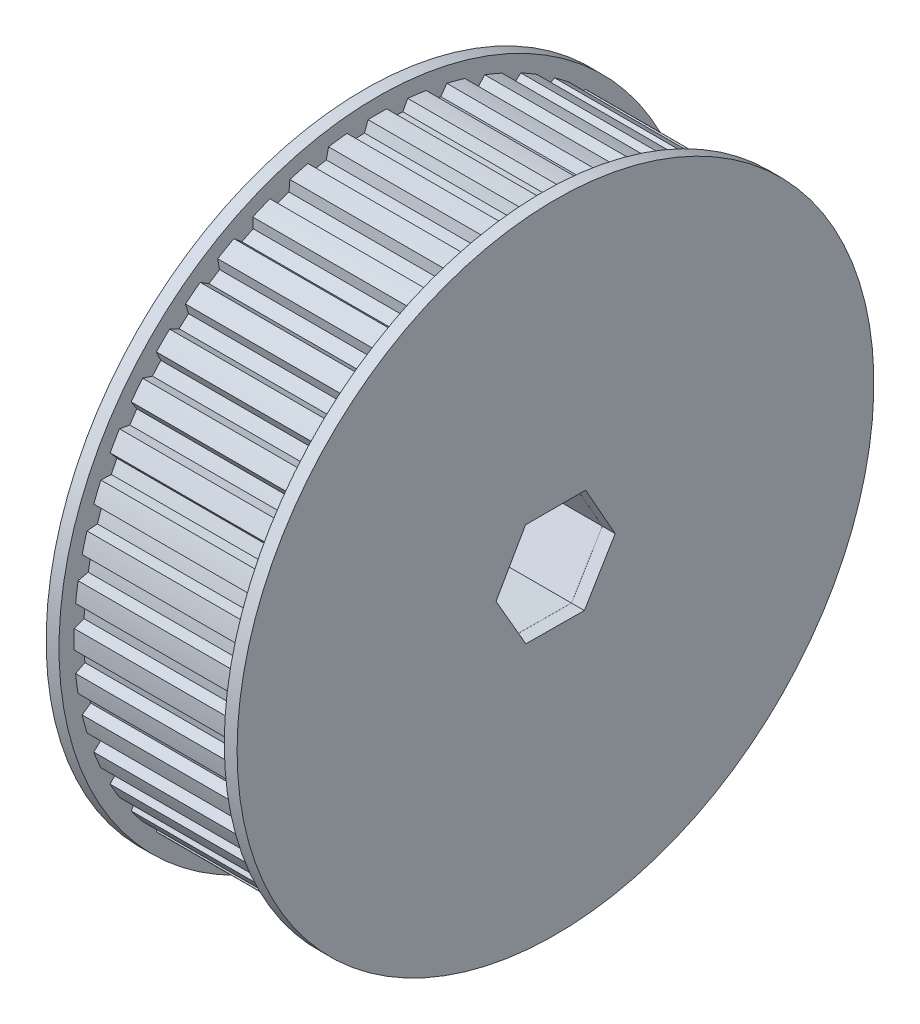
SolidWorks part; units mm, degrees
ref_plane "Front Plane" through (0, 0, 0) normal (0, 0, 1) x (1, 0, 0)
ref_plane "Top Plane" through (0, 0, 0) normal (0, 1, 0) x (1, 0, 0)
ref_plane "Right Plane" through (0, 0, 0) normal (1, 0, 0) x (0, 0, -1)
ref_plane "Plane1" through (0, 0, 0) normal (0, 0, -1) x (-1, 0, 0)
sketch "Sketch1" plane through (0, 0, 0) normal (0, 0, -1) x (-1, 0, 0)
  line L0 (-20.5, 37.625) -> (-20.5, 0)
  line L1 (-20.5, 0) -> (0, 0)
  line L2 (0, 0) -> (0, 37.625)
  line L3 (0, 37.625) -> (-20.5, 37.625)
  line L4 (-20.5, 0) -> (0, 0) construction
revolve "Revolve1" add sketch "Sketch1" angle 360 about L4 reverse direction yes
sketch "Sketch2" plane through (0, 0, 0) normal (-1, 0, 0) x (0, 0, 1)
  line L0 (-37.6072, 1.1569) -> (-36.3898, 1.6)
  line L1 (-36.2874, 3.1635) -> (-37.4365, 3.7617)
  arc A0 (-37.4365, 3.7617) -> (-37.6072, 1.1569) centre (0, 0) ccw
  arc A1 (-36.3898, 1.6) -> (-36.2874, 3.1635) centre (0, 0) cw
extrude "Cut-Extrude1" cut sketch "Sketch2" against normal through all
sketch "Sketch3" plane through (0, 0, 0) normal (-1, 0, 0) x (0, 0, 1)
  line L0 (-37.1345, 6.0557) -> (-35.8697, 6.3361)
  line L1 (-35.564, 7.8729) -> (-36.6252, 8.616)
  arc A0 (-36.6252, 8.616) -> (-37.1345, 6.0557) centre (0, 0) ccw
  arc A1 (-35.8697, 6.3361) -> (-35.564, 7.8729) centre (0, 0) cw
extrude "Cut-Extrude2" cut sketch "Sketch3" against normal through all
sketch "Sketch4" plane through (0, 0, 0) normal (-1, 0, 0) x (0, 0, 1)
  line L0 (-36.0263, 10.851) -> (-34.7358, 10.9639)
  line L1 (-34.2321, 12.4476) -> (-35.1873, 13.3228)
  arc A0 (-35.1873, 13.3228) -> (-36.0263, 10.851) centre (0, 0) ccw
  arc A1 (-34.7358, 10.9639) -> (-34.2321, 12.4476) centre (0, 0) cw
extrude "Cut-Extrude3" cut sketch "Sketch4" against normal through all
sketch "Sketch5" plane through (0, 0, 0) normal (-1, 0, 0) x (0, 0, 1)
  line L0 (-34.3018, 15.4605) -> (-33.0075, 15.404)
  line L1 (-32.3145, 16.8093) -> (-33.1473, 17.8017)
  arc A0 (-33.1473, 17.8017) -> (-34.3018, 15.4605) centre (0, 0) ccw
  arc A1 (-33.0075, 15.404) -> (-32.3145, 16.8093) centre (0, 0) cw
extrude "Cut-Extrude4" cut sketch "Sketch5" against normal through all
sketch "Sketch6" plane through (0, 0, 0) normal (-1, 0, 0) x (0, 0, 1)
  line L0 (-31.9903, 19.8055) -> (-30.7145, 19.5806)
  line L1 (-29.844, 20.8834) -> (-30.5401, 21.976)
  arc A0 (-30.5401, 21.976) -> (-31.9903, 19.8055) centre (0, 0) ccw
  arc A1 (-30.7145, 19.5806) -> (-29.844, 20.8834) centre (0, 0) cw
extrude "Cut-Extrude5" cut sketch "Sketch6" against normal through all
sketch "Sketch7" plane through (0, 0, 0) normal (-1, 0, 0) x (0, 0, 1)
  line L0 (-29.1315, 23.8117) -> (-27.896, 23.4221)
  line L1 (-26.8629, 24.6001) -> (-27.4104, 25.7743)
  arc A0 (-27.4104, 25.7743) -> (-29.1315, 23.8117) centre (0, 0) ccw
  arc A1 (-27.896, 23.4221) -> (-26.8629, 24.6001) centre (0, 0) cw
extrude "Cut-Extrude6" cut sketch "Sketch7" against normal through all
sketch "Sketch8" plane through (0, 0, 0) normal (-1, 0, 0) x (0, 0, 1)
  line L0 (-25.7743, 27.4104) -> (-24.6001, 26.8629)
  line L1 (-23.4221, 27.896) -> (-23.8117, 29.1315)
  arc A0 (-23.8117, 29.1315) -> (-25.7743, 27.4104) centre (0, 0) ccw
  arc A1 (-24.6001, 26.8629) -> (-23.4221, 27.896) centre (0, 0) cw
extrude "Cut-Extrude7" cut sketch "Sketch8" against normal through all
sketch "Sketch9" plane through (0, 0, 0) normal (-1, 0, 0) x (0, 0, 1)
  line L0 (-21.976, 30.5401) -> (-20.8834, 29.844)
  line L1 (-19.5806, 30.7145) -> (-19.8055, 31.9903)
  arc A0 (-19.8055, 31.9903) -> (-21.976, 30.5401) centre (0, 0) ccw
  arc A1 (-20.8834, 29.844) -> (-19.5806, 30.7145) centre (0, 0) cw
extrude "Cut-Extrude8" cut sketch "Sketch9" against normal through all
sketch "Sketch10" plane through (0, 0, 0) normal (-1, 0, 0) x (0, 0, 1)
  line L0 (-17.8017, 33.1473) -> (-16.8093, 32.3145)
  line L1 (-15.404, 33.0075) -> (-15.4605, 34.3018)
  arc A0 (-15.4605, 34.3018) -> (-17.8017, 33.1473) centre (0, 0) ccw
  arc A1 (-16.8093, 32.3145) -> (-15.404, 33.0075) centre (0, 0) cw
extrude "Cut-Extrude9" cut sketch "Sketch10" against normal through all
sketch "Sketch11" plane through (0, 0, 0) normal (-1, 0, 0) x (0, 0, 1)
  line L0 (-13.3228, 35.1873) -> (-12.4476, 34.2321)
  line L1 (-10.9639, 34.7358) -> (-10.851, 36.0263)
  arc A0 (-10.851, 36.0263) -> (-13.3228, 35.1873) centre (0, 0) ccw
  arc A1 (-12.4476, 34.2321) -> (-10.9639, 34.7358) centre (0, 0) cw
extrude "Cut-Extrude10" cut sketch "Sketch11" against normal through all
sketch "Sketch12" plane through (0, 0, 0) normal (-1, 0, 0) x (0, 0, 1)
  line L0 (-8.616, 36.6252) -> (-7.8729, 35.564)
  line L1 (-6.3361, 35.8697) -> (-6.0557, 37.1345)
  arc A0 (-6.0557, 37.1345) -> (-8.616, 36.6252) centre (0, 0) ccw
  arc A1 (-7.8729, 35.564) -> (-6.3361, 35.8697) centre (0, 0) cw
extrude "Cut-Extrude11" cut sketch "Sketch12" against normal through all
sketch "Sketch13" plane through (0, 0, 0) normal (-1, 0, 0) x (0, 0, 1)
  line L0 (-3.7617, 37.4365) -> (-3.1635, 36.2874)
  line L1 (-1.6, 36.3898) -> (-1.1569, 37.6072)
  arc A0 (-1.1569, 37.6072) -> (-3.7617, 37.4365) centre (0, 0) ccw
  arc A1 (-3.1635, 36.2874) -> (-1.6, 36.3898) centre (0, 0) cw
extrude "Cut-Extrude12" cut sketch "Sketch13" against normal through all
sketch "Sketch14" plane through (0, 0, 0) normal (-1, 0, 0) x (0, 0, 1)
  line L0 (1.1569, 37.6072) -> (1.6, 36.3898)
  line L1 (3.1635, 36.2874) -> (3.7617, 37.4365)
  arc A0 (3.7617, 37.4365) -> (1.1569, 37.6072) centre (0, 0) ccw
  arc A1 (1.6, 36.3898) -> (3.1635, 36.2874) centre (0, 0) cw
extrude "Cut-Extrude13" cut sketch "Sketch14" against normal through all
sketch "Sketch15" plane through (0, 0, 0) normal (-1, 0, 0) x (0, 0, 1)
  line L0 (6.0557, 37.1345) -> (6.3361, 35.8697)
  line L1 (7.8729, 35.564) -> (8.616, 36.6252)
  arc A0 (8.616, 36.6252) -> (6.0557, 37.1345) centre (0, 0) ccw
  arc A1 (6.3361, 35.8697) -> (7.8729, 35.564) centre (0, 0) cw
extrude "Cut-Extrude14" cut sketch "Sketch15" against normal through all
sketch "Sketch16" plane through (0, 0, 0) normal (-1, 0, 0) x (0, 0, 1)
  line L0 (10.851, 36.0263) -> (10.9639, 34.7358)
  line L1 (12.4476, 34.2321) -> (13.3228, 35.1873)
  arc A0 (13.3228, 35.1873) -> (10.851, 36.0263) centre (0, 0) ccw
  arc A1 (10.9639, 34.7358) -> (12.4476, 34.2321) centre (0, 0) cw
extrude "Cut-Extrude15" cut sketch "Sketch16" against normal through all
sketch "Sketch17" plane through (0, 0, 0) normal (-1, 0, 0) x (0, 0, 1)
  line L0 (15.4605, 34.3018) -> (15.404, 33.0075)
  line L1 (16.8093, 32.3145) -> (17.8017, 33.1473)
  arc A0 (17.8017, 33.1473) -> (15.4605, 34.3018) centre (0, 0) ccw
  arc A1 (15.404, 33.0075) -> (16.8093, 32.3145) centre (0, 0) cw
extrude "Cut-Extrude16" cut sketch "Sketch17" against normal through all
sketch "Sketch18" plane through (0, 0, 0) normal (-1, 0, 0) x (0, 0, 1)
  line L0 (19.8055, 31.9903) -> (19.5806, 30.7145)
  line L1 (20.8834, 29.844) -> (21.976, 30.5401)
  arc A0 (21.976, 30.5401) -> (19.8055, 31.9903) centre (0, 0) ccw
  arc A1 (19.5806, 30.7145) -> (20.8834, 29.844) centre (0, 0) cw
extrude "Cut-Extrude17" cut sketch "Sketch18" against normal through all
sketch "Sketch19" plane through (0, 0, 0) normal (-1, 0, 0) x (0, 0, 1)
  line L0 (23.8117, 29.1315) -> (23.4221, 27.896)
  line L1 (24.6001, 26.8629) -> (25.7743, 27.4104)
  arc A0 (25.7743, 27.4104) -> (23.8117, 29.1315) centre (0, 0) ccw
  arc A1 (23.4221, 27.896) -> (24.6001, 26.8629) centre (0, 0) cw
extrude "Cut-Extrude18" cut sketch "Sketch19" against normal through all
sketch "Sketch20" plane through (0, 0, 0) normal (-1, 0, 0) x (0, 0, 1)
  line L0 (27.4104, 25.7743) -> (26.8629, 24.6001)
  line L1 (27.896, 23.4221) -> (29.1315, 23.8117)
  arc A0 (29.1315, 23.8117) -> (27.4104, 25.7743) centre (0, 0) ccw
  arc A1 (26.8629, 24.6001) -> (27.896, 23.4221) centre (0, 0) cw
extrude "Cut-Extrude19" cut sketch "Sketch20" against normal through all
sketch "Sketch21" plane through (0, 0, 0) normal (-1, 0, 0) x (0, 0, 1)
  line L0 (30.5401, 21.976) -> (29.844, 20.8834)
  line L1 (30.7145, 19.5806) -> (31.9903, 19.8055)
  arc A0 (31.9903, 19.8055) -> (30.5401, 21.976) centre (0, 0) ccw
  arc A1 (29.844, 20.8834) -> (30.7145, 19.5806) centre (0, 0) cw
extrude "Cut-Extrude20" cut sketch "Sketch21" against normal through all
sketch "Sketch22" plane through (0, 0, 0) normal (-1, 0, 0) x (0, 0, 1)
  line L0 (33.1473, 17.8017) -> (32.3145, 16.8093)
  line L1 (33.0075, 15.404) -> (34.3018, 15.4605)
  arc A0 (34.3018, 15.4605) -> (33.1473, 17.8017) centre (0, 0) ccw
  arc A1 (32.3145, 16.8093) -> (33.0075, 15.404) centre (0, 0) cw
extrude "Cut-Extrude21" cut sketch "Sketch22" against normal through all
sketch "Sketch23" plane through (0, 0, 0) normal (-1, 0, 0) x (0, 0, 1)
  line L0 (35.1873, 13.3228) -> (34.2321, 12.4476)
  line L1 (34.7358, 10.9639) -> (36.0263, 10.851)
  arc A0 (36.0263, 10.851) -> (35.1873, 13.3228) centre (0, 0) ccw
  arc A1 (34.2321, 12.4476) -> (34.7358, 10.9639) centre (0, 0) cw
extrude "Cut-Extrude22" cut sketch "Sketch23" against normal through all
sketch "Sketch24" plane through (0, 0, 0) normal (-1, 0, 0) x (0, 0, 1)
  line L0 (36.6252, 8.616) -> (35.564, 7.8729)
  line L1 (35.8697, 6.3361) -> (37.1345, 6.0557)
  arc A0 (37.1345, 6.0557) -> (36.6252, 8.616) centre (0, 0) ccw
  arc A1 (35.564, 7.8729) -> (35.8697, 6.3361) centre (0, 0) cw
extrude "Cut-Extrude23" cut sketch "Sketch24" against normal through all
sketch "Sketch25" plane through (0, 0, 0) normal (-1, 0, 0) x (0, 0, 1)
  line L0 (37.4365, 3.7617) -> (36.2874, 3.1635)
  line L1 (36.3898, 1.6) -> (37.6072, 1.1569)
  arc A0 (37.6072, 1.1569) -> (37.4365, 3.7617) centre (0, 0) ccw
  arc A1 (36.2874, 3.1635) -> (36.3898, 1.6) centre (0, 0) cw
extrude "Cut-Extrude24" cut sketch "Sketch25" against normal through all
sketch "Sketch26" plane through (0, 0, 0) normal (-1, 0, 0) x (0, 0, 1)
  line L0 (37.6072, -1.1569) -> (36.3898, -1.6)
  line L1 (36.2874, -3.1635) -> (37.4365, -3.7617)
  arc A0 (37.4365, -3.7617) -> (37.6072, -1.1569) centre (0, 0) ccw
  arc A1 (36.3898, -1.6) -> (36.2874, -3.1635) centre (0, 0) cw
extrude "Cut-Extrude25" cut sketch "Sketch26" against normal through all
sketch "Sketch27" plane through (0, 0, 0) normal (-1, 0, 0) x (0, 0, 1)
  line L0 (37.1345, -6.0557) -> (35.8697, -6.3361)
  line L1 (35.564, -7.8729) -> (36.6252, -8.616)
  arc A0 (36.6252, -8.616) -> (37.1345, -6.0557) centre (0, 0) ccw
  arc A1 (35.8697, -6.3361) -> (35.564, -7.8729) centre (0, 0) cw
extrude "Cut-Extrude26" cut sketch "Sketch27" against normal through all
sketch "Sketch28" plane through (0, 0, 0) normal (-1, 0, 0) x (0, 0, 1)
  line L0 (36.0263, -10.851) -> (34.7358, -10.9639)
  line L1 (34.2321, -12.4476) -> (35.1873, -13.3228)
  arc A0 (35.1873, -13.3228) -> (36.0263, -10.851) centre (0, 0) ccw
  arc A1 (34.7358, -10.9639) -> (34.2321, -12.4476) centre (0, 0) cw
extrude "Cut-Extrude27" cut sketch "Sketch28" against normal through all
sketch "Sketch29" plane through (0, 0, 0) normal (-1, 0, 0) x (0, 0, 1)
  line L0 (34.3018, -15.4605) -> (33.0075, -15.404)
  line L1 (32.3145, -16.8093) -> (33.1473, -17.8017)
  arc A0 (33.1473, -17.8017) -> (34.3018, -15.4605) centre (0, 0) ccw
  arc A1 (33.0075, -15.404) -> (32.3145, -16.8093) centre (0, 0) cw
extrude "Cut-Extrude28" cut sketch "Sketch29" against normal through all
sketch "Sketch30" plane through (0, 0, 0) normal (-1, 0, 0) x (0, 0, 1)
  line L0 (31.9903, -19.8055) -> (30.7145, -19.5806)
  line L1 (29.844, -20.8834) -> (30.5401, -21.976)
  arc A0 (30.5401, -21.976) -> (31.9903, -19.8055) centre (0, 0) ccw
  arc A1 (30.7145, -19.5806) -> (29.844, -20.8834) centre (0, 0) cw
extrude "Cut-Extrude29" cut sketch "Sketch30" against normal through all
sketch "Sketch31" plane through (0, 0, 0) normal (-1, 0, 0) x (0, 0, 1)
  line L0 (29.1315, -23.8117) -> (27.896, -23.4221)
  line L1 (26.8629, -24.6001) -> (27.4104, -25.7743)
  arc A0 (27.4104, -25.7743) -> (29.1315, -23.8117) centre (0, 0) ccw
  arc A1 (27.896, -23.4221) -> (26.8629, -24.6001) centre (0, 0) cw
extrude "Cut-Extrude30" cut sketch "Sketch31" against normal through all
sketch "Sketch32" plane through (0, 0, 0) normal (-1, 0, 0) x (0, 0, 1)
  line L0 (25.7743, -27.4104) -> (24.6001, -26.8629)
  line L1 (23.4221, -27.896) -> (23.8117, -29.1315)
  arc A0 (23.8117, -29.1315) -> (25.7743, -27.4104) centre (0, 0) ccw
  arc A1 (24.6001, -26.8629) -> (23.4221, -27.896) centre (0, 0) cw
extrude "Cut-Extrude31" cut sketch "Sketch32" against normal through all
sketch "Sketch33" plane through (0, 0, 0) normal (-1, 0, 0) x (0, 0, 1)
  line L0 (21.976, -30.5401) -> (20.8834, -29.844)
  line L1 (19.5806, -30.7145) -> (19.8055, -31.9903)
  arc A0 (19.8055, -31.9903) -> (21.976, -30.5401) centre (0, 0) ccw
  arc A1 (20.8834, -29.844) -> (19.5806, -30.7145) centre (0, 0) cw
extrude "Cut-Extrude32" cut sketch "Sketch33" against normal through all
sketch "Sketch34" plane through (0, 0, 0) normal (-1, 0, 0) x (0, 0, 1)
  line L0 (17.8017, -33.1473) -> (16.8093, -32.3145)
  line L1 (15.404, -33.0075) -> (15.4605, -34.3018)
  arc A0 (15.4605, -34.3018) -> (17.8017, -33.1473) centre (0, 0) ccw
  arc A1 (16.8093, -32.3145) -> (15.404, -33.0075) centre (0, 0) cw
extrude "Cut-Extrude33" cut sketch "Sketch34" against normal through all
sketch "Sketch35" plane through (0, 0, 0) normal (-1, 0, 0) x (0, 0, 1)
  line L0 (13.3228, -35.1873) -> (12.4476, -34.2321)
  line L1 (10.9639, -34.7358) -> (10.851, -36.0263)
  arc A0 (10.851, -36.0263) -> (13.3228, -35.1873) centre (0, 0) ccw
  arc A1 (12.4476, -34.2321) -> (10.9639, -34.7358) centre (0, 0) cw
extrude "Cut-Extrude34" cut sketch "Sketch35" against normal through all
sketch "Sketch36" plane through (0, 0, 0) normal (-1, 0, 0) x (0, 0, 1)
  line L0 (8.616, -36.6252) -> (7.8729, -35.564)
  line L1 (6.3361, -35.8697) -> (6.0557, -37.1345)
  arc A0 (6.0557, -37.1345) -> (8.616, -36.6252) centre (0, 0) ccw
  arc A1 (7.8729, -35.564) -> (6.3361, -35.8697) centre (0, 0) cw
extrude "Cut-Extrude35" cut sketch "Sketch36" against normal through all
sketch "Sketch37" plane through (0, 0, 0) normal (-1, 0, 0) x (0, 0, 1)
  line L0 (3.7617, -37.4365) -> (3.1635, -36.2874)
  line L1 (1.6, -36.3898) -> (1.1569, -37.6072)
  arc A0 (1.1569, -37.6072) -> (3.7617, -37.4365) centre (0, 0) ccw
  arc A1 (3.1635, -36.2874) -> (1.6, -36.3898) centre (0, 0) cw
extrude "Cut-Extrude36" cut sketch "Sketch37" against normal through all
sketch "Sketch38" plane through (0, 0, 0) normal (-1, 0, 0) x (0, 0, 1)
  line L0 (-1.1569, -37.6072) -> (-1.6, -36.3898)
  line L1 (-3.1635, -36.2874) -> (-3.7617, -37.4365)
  arc A0 (-3.7617, -37.4365) -> (-1.1569, -37.6072) centre (0, 0) ccw
  arc A1 (-1.6, -36.3898) -> (-3.1635, -36.2874) centre (0, 0) cw
extrude "Cut-Extrude37" cut sketch "Sketch38" against normal through all
sketch "Sketch39" plane through (0, 0, 0) normal (-1, 0, 0) x (0, 0, 1)
  line L0 (-6.0557, -37.1345) -> (-6.3361, -35.8697)
  line L1 (-7.8729, -35.564) -> (-8.616, -36.6252)
  arc A0 (-8.616, -36.6252) -> (-6.0557, -37.1345) centre (0, 0) ccw
  arc A1 (-6.3361, -35.8697) -> (-7.8729, -35.564) centre (0, 0) cw
extrude "Cut-Extrude38" cut sketch "Sketch39" against normal through all
sketch "Sketch40" plane through (0, 0, 0) normal (-1, 0, 0) x (0, 0, 1)
  line L0 (-10.851, -36.0263) -> (-10.9639, -34.7358)
  line L1 (-12.4476, -34.2321) -> (-13.3228, -35.1873)
  arc A0 (-13.3228, -35.1873) -> (-10.851, -36.0263) centre (0, 0) ccw
  arc A1 (-10.9639, -34.7358) -> (-12.4476, -34.2321) centre (0, 0) cw
extrude "Cut-Extrude39" cut sketch "Sketch40" against normal through all
sketch "Sketch41" plane through (0, 0, 0) normal (-1, 0, 0) x (0, 0, 1)
  line L0 (-15.4605, -34.3018) -> (-15.404, -33.0075)
  line L1 (-16.8093, -32.3145) -> (-17.8017, -33.1473)
  arc A0 (-17.8017, -33.1473) -> (-15.4605, -34.3018) centre (0, 0) ccw
  arc A1 (-15.404, -33.0075) -> (-16.8093, -32.3145) centre (0, 0) cw
extrude "Cut-Extrude40" cut sketch "Sketch41" against normal through all
sketch "Sketch42" plane through (0, 0, 0) normal (-1, 0, 0) x (0, 0, 1)
  line L0 (-19.8055, -31.9903) -> (-19.5806, -30.7145)
  line L1 (-20.8834, -29.844) -> (-21.976, -30.5401)
  arc A0 (-21.976, -30.5401) -> (-19.8055, -31.9903) centre (0, 0) ccw
  arc A1 (-19.5806, -30.7145) -> (-20.8834, -29.844) centre (0, 0) cw
extrude "Cut-Extrude41" cut sketch "Sketch42" against normal through all
sketch "Sketch43" plane through (0, 0, 0) normal (-1, 0, 0) x (0, 0, 1)
  line L0 (-23.8117, -29.1315) -> (-23.4221, -27.896)
  line L1 (-24.6001, -26.8629) -> (-25.7743, -27.4104)
  arc A0 (-25.7743, -27.4104) -> (-23.8117, -29.1315) centre (0, 0) ccw
  arc A1 (-23.4221, -27.896) -> (-24.6001, -26.8629) centre (0, 0) cw
extrude "Cut-Extrude42" cut sketch "Sketch43" against normal through all
sketch "Sketch44" plane through (0, 0, 0) normal (-1, 0, 0) x (0, 0, 1)
  line L0 (-27.4104, -25.7743) -> (-26.8629, -24.6001)
  line L1 (-27.896, -23.4221) -> (-29.1315, -23.8117)
  arc A0 (-29.1315, -23.8117) -> (-27.4104, -25.7743) centre (0, 0) ccw
  arc A1 (-26.8629, -24.6001) -> (-27.896, -23.4221) centre (0, 0) cw
extrude "Cut-Extrude43" cut sketch "Sketch44" against normal through all
sketch "Sketch45" plane through (0, 0, 0) normal (-1, 0, 0) x (0, 0, 1)
  line L0 (-30.5401, -21.976) -> (-29.844, -20.8834)
  line L1 (-30.7145, -19.5806) -> (-31.9903, -19.8055)
  arc A0 (-31.9903, -19.8055) -> (-30.5401, -21.976) centre (0, 0) ccw
  arc A1 (-29.844, -20.8834) -> (-30.7145, -19.5806) centre (0, 0) cw
extrude "Cut-Extrude44" cut sketch "Sketch45" against normal through all
sketch "Sketch46" plane through (0, 0, 0) normal (-1, 0, 0) x (0, 0, 1)
  line L0 (-33.1473, -17.8017) -> (-32.3145, -16.8093)
  line L1 (-33.0075, -15.404) -> (-34.3018, -15.4605)
  arc A0 (-34.3018, -15.4605) -> (-33.1473, -17.8017) centre (0, 0) ccw
  arc A1 (-32.3145, -16.8093) -> (-33.0075, -15.404) centre (0, 0) cw
extrude "Cut-Extrude45" cut sketch "Sketch46" against normal through all
sketch "Sketch47" plane through (0, 0, 0) normal (-1, 0, 0) x (0, 0, 1)
  line L0 (-35.1873, -13.3228) -> (-34.2321, -12.4476)
  line L1 (-34.7358, -10.9639) -> (-36.0263, -10.851)
  arc A0 (-36.0263, -10.851) -> (-35.1873, -13.3228) centre (0, 0) ccw
  arc A1 (-34.2321, -12.4476) -> (-34.7358, -10.9639) centre (0, 0) cw
extrude "Cut-Extrude46" cut sketch "Sketch47" against normal through all
sketch "Sketch48" plane through (0, 0, 0) normal (-1, 0, 0) x (0, 0, 1)
  line L0 (-36.6252, -8.616) -> (-35.564, -7.8729)
  line L1 (-35.8697, -6.3361) -> (-37.1345, -6.0557)
  arc A0 (-37.1345, -6.0557) -> (-36.6252, -8.616) centre (0, 0) ccw
  arc A1 (-35.564, -7.8729) -> (-35.8697, -6.3361) centre (0, 0) cw
extrude "Cut-Extrude47" cut sketch "Sketch48" against normal through all
sketch "Sketch49" plane through (0, 0, 0) normal (-1, 0, 0) x (0, 0, 1)
  line L0 (-37.4365, -3.7617) -> (-36.2874, -3.1635)
  line L1 (-36.3898, -1.6) -> (-37.6072, -1.1569)
  arc A0 (-37.6072, -1.1569) -> (-37.4365, -3.7617) centre (0, 0) ccw
  arc A1 (-36.2874, -3.1635) -> (-36.3898, -1.6) centre (0, 0) cw
extrude "Cut-Extrude48" cut sketch "Sketch49" against normal through all
sketch "Sketch50" plane through (0, 0, 0) normal (0, 0, 1) x (1, 0, 0)
  line L0 (-1.5906, 39.5) -> (-1.5906, 0)
  line L1 (-1.5906, 0) -> (0.0026, 0)
  line L2 (0.0026, 0) -> (0.0026, 39.5)
  line L3 (0.0026, 39.5) -> (-1.5906, 39.5)
  line L4 (-1.5906, 0) -> (0.0026, 0) construction
revolve "Revolve2" add sketch "Sketch50" angle 360 about L4 reverse direction yes
hole_wizard "Ø2.0 (2) Diameter Hole1" positions "Sketch52" profile "Sketch51" hole size "Ø2.0" standard "ANSI Metric"
sketch "Sketch52" plane through (-1.5906, 0, 0) normal (-1, 0, 0) x (0, 0, 1)
  point P0 (0, 0)
sketch "Sketch51" plane through (-1.5906, 0, 0) normal (0, 1, 0) x (0, 0, 1)
  line L0 (0, 0) -> (0, 22.0906)
  line L1 (0, 22.0906) -> (1, 22.0906)
  line L2 (1, 22.0906) -> (1, 0)
  line L5 (1, 0) -> (0, 0)
  line L11 (0, -6.35) -> (0, 107.95) construction
  dimension "Thru Hole Dia." = 2
  dimension "Thru Hole Depth" = 22.0906
sketch "Sketch54" plane through (0, 0, 0) normal (1, 0, 0) x (0, 0, -1)
  line L0 (-3.7161, 6.4008) -> (-7.3705, 0)
  line L1 (-7.3705, 0) -> (-3.6748, -6.4008)
  line L2 (-3.6748, -6.4008) -> (3.5818, -6.4534)
  line L3 (3.5818, -6.4534) -> (7.4109, -0.1072)
  line L4 (7.4109, -0.1072) -> (3.7368, 6.4008)
  line L5 (3.7368, 6.4008) -> (-3.7161, 6.4008)
sketch "Sketch57" plane through (0, 0, 0) normal (0, 0, 1) x (1, 0, 0)
  line L0 (20.5068, 39.5) -> (20.5068, 0)
  line L1 (20.5068, 0) -> (22.1, 0)
  line L2 (22.1, 0) -> (22.1, 39.5)
  line L3 (22.1, 39.5) -> (20.5068, 39.5)
  line L4 (20.5068, 0) -> (22.1, 0) construction
revolve "Revolve5" add sketch "Sketch57" angle 360 about L4
extrude "Cut-Extrude50" cut sketch "Sketch54" against normal through all both and the other way through all
